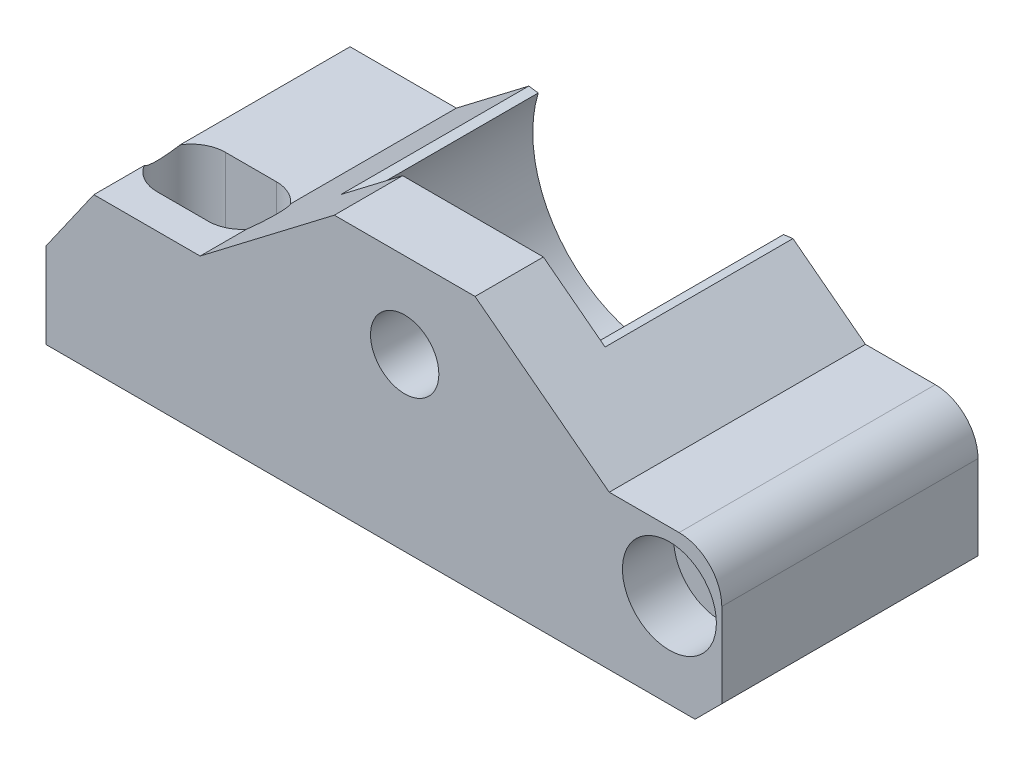
SolidWorks part; units mm, degrees
material "6061-O (SS)"
ref_plane "Piano frontale" through (0, 0, 0) normal (0, 0, 1) x (1, 0, 0)
ref_plane "Piano superiore" through (0, 0, 0) normal (0, 1, 0) x (1, 0, 0)
ref_plane "Piano destro" through (0, 0, 0) normal (1, 0, 0) x (0, 0, -1)
sketch "Schizzo2" plane through (0, 0, 0) normal (0, 0, 1) x (1, 0, 0)
  line L0 (-40, 0) -> (-2, 0)
  line L1 (-40, 0) -> (-40, 9)
  line L2 (-19, 0) -> (-19, 25.5566) construction
  line L3 (-40, 9) -> (-30.9754, 9)
  line L4 (-30.9754, 9) -> (-23.1199, 15)
  line L5 (-23.1199, 15) -> (-14.8801, 15)
  line L6 (-7.0246, 9) -> (-14.8801, 15)
  line L7 (-0.4334, 9) -> (-7.0246, 9)
  line L8 (-0.4334, 1.5666) -> (-2, 0)
  line L11 (-0.4334, 9) -> (-0.4334, 1.5666)
  circle A0 centre (-19, 10) radius 2
  circle A1 centre (-3.5, 5.5) radius 1.3432
  point P0 (-40, 0)
  point P1 (2, 0)
  point P10 (-19, 15)
  dimension "D3" = 4
  dimension "D4" = 15
  dimension "D1" = 42
  dimension "D2" = 9
  dimension "D5" = 10
  dimension "D6" = 15.5
  dimension "D7" = 5.5
  dimension "D9" = 4
extrude "Estrusione-Estrusione1" add sketch "Schizzo2" against normal blind 15
sketch "Schizzo3" plane through (0, 0, -15) normal (0, 0, -1) x (-1, 0, 0)
  circle A0 centre (19, 10) radius 7.5
  circle A1 centre (19, 10) radius 2 construction
  dimension "D1" = 15
extrude "Taglio-Estrusione1" cut sketch "Schizzo3" against normal blind 11
sketch "Schizzo4" plane through (0, 0, 0) normal (0, 0, 1) x (1, 0, 0)
  circle A0 centre (-3.5, 5.5) radius 2.75
  dimension "D1" = 5.5
extrude "Taglio-Estrusione2" cut sketch "Schizzo4" against normal blind 3
chamfer "Smusso3" distance 1 angle 45 2 edges at (-12.0614, 12.8471, -9.5) (-25.9386, 12.8471, -9.5) first distance on face at (-11.322, 12.2824, -6.3333) first distance on face at (-26.678, 12.2824, -6.3333)
fillet "Raccordo1" radius 2.5 1 edges at (-0.4334, 9, -7.5)
chamfer "Smusso4" distance 4 angle 35 1 edges at (-40, 9, -7.5) first distance on face at (-40, 4.5, -7.5)
sketch "Schizzo5" plane through (0, 0, 0) normal (0, -1, 0) x (1, 0, 0)
  line L0 (0, -4) -> (39.5666, -4) construction
  line L2 (-35.5, -4) -> (-32.5, -4) construction
  line L3 (-40, 0) -> (-2, 0) construction
  line L4 (-35.5, -2) -> (-32.5, -2)
  line L5 (-35.5, -6) -> (-32.5, -6)
  arc A1 (-35.5, -2) -> (-35.5, -6) centre (-35.5, -4) ccw
  arc A2 (-32.5, -6) -> (-32.5, -2) centre (-32.5, -4) ccw
  point P10 (-34, -4)
  dimension "D2" = 4
  dimension "D4" = 4
  dimension "D5" = 3
extrude "Taglio-Estrusione3" cut sketch "Schizzo5" against normal through all
